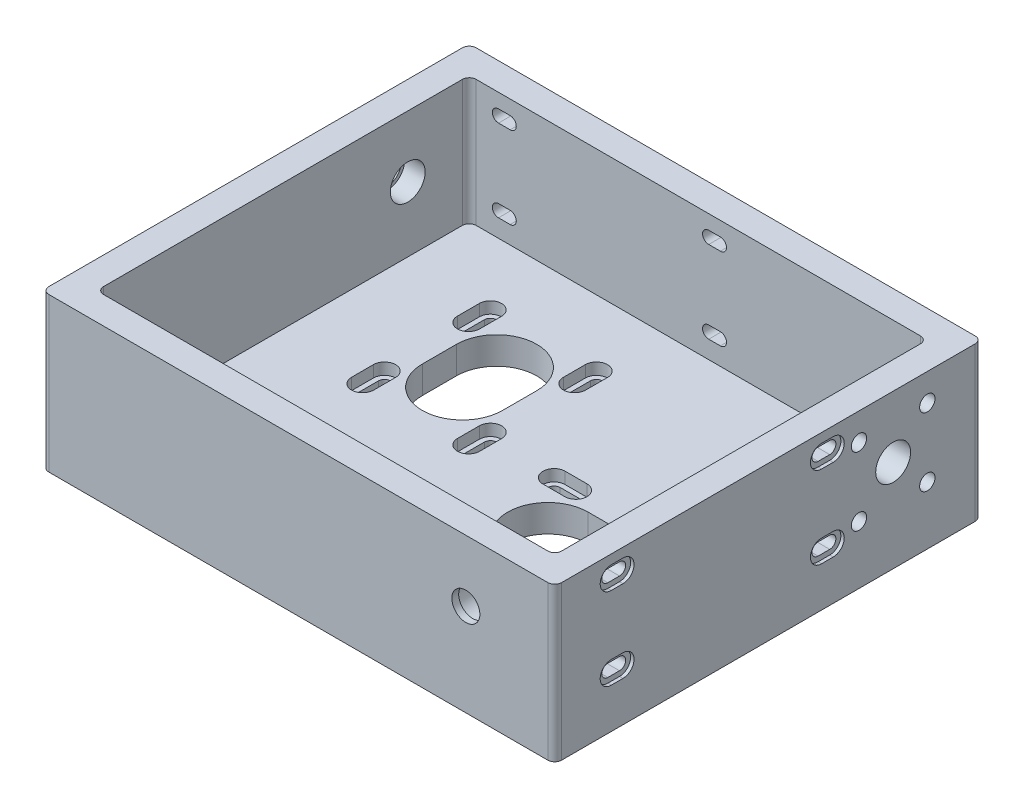
SolidWorks part; units mm, degrees
ref_plane "前基準面" through (0, 0, 0) normal (0, 0, 1) x (1, 0, 0)
ref_plane "上基準面" through (0, 0, 0) normal (0, 1, 0) x (1, 0, 0)
ref_plane "右基準面" through (0, 0, 0) normal (1, 0, 0) x (0, 0, -1)
sketch "草圖1" plane through (0, 0, 0) normal (0, 1, 0) x (1, 0, 0)
  line L1 (-75, -62.5) -> (75, -62.5)
  line L2 (-75, -62.5) -> (-75, 62.5)
  line L3 (-75, 62.5) -> (75, 62.5)
  line L4 (75, -62.5) -> (75, 62.5)
  line L5 (-75, -62.5) -> (75, 62.5) construction
  line L6 (-75, 62.5) -> (75, -62.5) construction
  point P0 (0, 0)
  dimension "D1" = 125
  dimension "D2" = 150
extrude "填料-伸長1" add sketch "草圖1" along normal blind 45
shell "薄殼1" thickness 8 removed face at (0, 45, 0)
sketch "草圖5" plane through (0, 0, 62.5) normal (0, 0, 1) x (1, 0, 0)
  line L0 (67, 45) -> (67, 8) construction
  line L3 (-67, 45) -> (67, 45) construction
  circle A0 centre (49, 27) radius 5.1
  dimension "D3" = 10.2
  dimension "D1" = 18
  dimension "D2" = 18
extrude "除料-伸長1" cut sketch "草圖5" against normal up to next
sketch "草圖6" plane through (-75, 0, 0) normal (-1, 0, 0) x (0, 0, 1)
  line L0 (54.5, 32.1) -> (54.5, 21.9) construction
  line L1 (54.5, 32.1) -> (54.5, 21.9) construction
  line L2 (54.5, 27) -> (-36.5, 27) construction
  line L3 (-54.5, 45) -> (-54.5, 8) construction
  line L4 (-36.5, 32.1) -> (-36.5, 21.9) construction
  circle A0 centre (-36.5, 27) radius 5.1
  dimension "D1" = 18
extrude "除料-伸長2" cut sketch "草圖6" against normal through all
sketch "草圖7" plane through (0, 8, 0) normal (0, 1, 0) x (1, 0, 0)
  line L0 (-26, 21.5) -> (-26, 11.5) construction
  line L1 (-14.25, 21.5) -> (-14.25, 11.5)
  line L2 (-37.75, 21.5) -> (-37.75, 11.5)
  line L3 (24, -13.5) -> (34, -13.5) construction
  line L4 (24, -1.75) -> (34, -1.75)
  line L5 (24, -25.25) -> (34, -25.25)
  arc A0 (-14.25, 21.5) -> (-37.75, 21.5) centre (-26, 21.5) ccw
  arc A1 (-37.75, 11.5) -> (-14.25, 11.5) centre (-26, 11.5) ccw
  arc A3 (24, -1.75) -> (24, -25.25) centre (24, -13.5) ccw
  arc A4 (34, -25.25) -> (34, -1.75) centre (34, -13.5) ccw
  circle A5 centre (29, -13.5) radius 11.75 construction
  point P2 (-26, 16.5)
  point P12 (29, -13.5)
  dimension "D1" = 10
extrude "除料-伸長3" cut sketch "草圖7" against normal through all
hole_wizard "M3 六角承窩頭蓋螺釘的柱孔2" positions "草圖8" profile "草圖9" size "M3" standard "ISO" slot yes
sketch "草圖8" plane through (0, 8, 0) normal (0, 1, 0) x (1, 0, 0)
  line L0 (-10.5, 27) -> (-10.5, 37) construction
  point P0 (-10.5, 32)
  point P5 (-10.5, 1)
  point P8 (-41.5, 1)
  point P11 (-41.5, 32)
  dimension "D1" = 10
sketch "草圖9" plane through (-10.5, 8, -32) normal (1, 0, 0) x (0, 0, 1)
  line L0 (0, 0) -> (0, 11.0815)
  line L1 (0, 11.0815) -> (1.8, 10)
  line L2 (1.8, 10) -> (1.8, 3.4)
  line L3 (1.8, 3.4) -> (3.25, 3.4)
  line L4 (3.25, 3.4) -> (3.25, 0)
  line L5 (3.25, 0) -> (0, 0)
  line L10 (0, 11.0815) -> (-1.8, 10) construction
  line L11 (0, -6.35) -> (0, 107.95) construction
  dimension "鑽孔直徑" = 3.6
  dimension "鑽孔深度" = 10
  dimension "柱孔直徑" = 6.5
  dimension "柱孔深度" = 3.4
  dimension "導頭角度" = 118
hole_wizard "M3 六角承窩頭蓋螺釘的柱孔1" positions "草圖10" profile "草圖11" size "M3" standard "ISO" slot yes end condition through all
sketch "草圖10" plane through (0, 8, 0) normal (0, 1, 0) x (1, 0, 0)
  line L0 (39.5, 2) -> (49.5, 2) construction
  point P0 (44.5, 2)
  point P4 (44.5, -29)
  point P7 (13.5, 2)
  point P10 (13.5, -29)
  dimension "D1" = 10
sketch "草圖11" plane through (44.5, 8, -2) normal (1, 0, 0) x (0, 0, 1)
  line L0 (0, 0) -> (0, 8)
  line L1 (0, 8) -> (1.8, 8)
  line L3 (1.8, 8) -> (1.8, 3.4)
  line L4 (1.8, 3.4) -> (3.25, 3.4)
  line L5 (3.25, 3.4) -> (3.25, 0)
  line L7 (3.25, 0) -> (0, 0)
  line L11 (0, -6.35) -> (0, 107.95) construction
  dimension "貫穿孔直徑" = 3.6
  dimension "貫穿孔深度" = 8
  dimension "柱孔直徑" = 6.5
  dimension "柱孔深度" = 3.4
hole_wizard "M3 六角承窩頭蓋螺釘的柱孔4" positions "草圖12" profile "草圖14" size "M3" standard "ISO" slot yes end condition up to next
sketch "草圖12" plane through (0, 0, -62.5) normal (0, 0, -1) x (-1, 0, 0)
  line L0 (60.25, 39) -> (53.25, 39) construction
  point P0 (56.75, 39)
  point P3 (56.75, 15)
  point P9 (-4.75, 39)
  point P12 (-4.75, 15)
  dimension "D1" = 7
sketch "草圖14" plane through (-56.75, 39, -62.5) normal (1, 0, 0) x (0, 1, 0)
  line L0 (0, 0) -> (0, 8)
  line L1 (0, 8) -> (1.8, 8)
  line L3 (1.8, 8) -> (1.8, 1)
  line L4 (1.8, 1) -> (3.25, 1)
  line L5 (3.25, 1) -> (3.25, 0)
  line L7 (3.25, 0) -> (0, 0)
  line L11 (0, -6.35) -> (0, 107.95) construction
  dimension "貫穿孔直徑" = 3.6
  dimension "貫穿孔深度" = 8
  dimension "柱孔直徑" = 6.5
  dimension "柱孔深度" = 1
hole_wizard "M3 六角承窩頭蓋螺釘的柱孔5" positions "草圖15" profile "草圖16" size "M3" standard "ISO" slot yes end condition up to next
sketch "草圖15" plane through (75, 0, 0) normal (1, 0, 0) x (0, 0, -1)
  line L0 (20.75, 39) -> (13.75, 39) construction
  point P0 (17.25, 39)
  point P5 (17.25, 15)
  point P8 (-44.25, 15)
  point P11 (-44.25, 39)
  dimension "D1" = 7
sketch "草圖16" plane through (75, 39, -17.25) normal (0, 1, 0) x (0, 0, -1)
  line L0 (0, 0) -> (0, 8)
  line L1 (0, 8) -> (1.8, 8)
  line L3 (1.8, 8) -> (1.8, 1)
  line L4 (1.8, 1) -> (3.25, 1)
  line L5 (3.25, 1) -> (3.25, 0)
  line L7 (3.25, 0) -> (0, 0)
  line L11 (0, -6.35) -> (0, 107.95) construction
  dimension "貫穿孔直徑" = 3.6
  dimension "貫穿孔深度" = 8
  dimension "柱孔直徑" = 6.5
  dimension "柱孔深度" = 1
fillet "圓角1" radius 2 4 edges at (67, 26.5, 54.5) (67, 26.5, -54.5) (-67, 26.5, -54.5) (-67, 26.5, 54.5)
fillet "圓角2" radius 2 4 edges at (75, 22.5, 62.5) (-75, 22.5, -62.5) (75, 22.5, -62.5) (-75, 22.5, 62.5)
sketch "草圖17" plane through (75, 0, 0) normal (1, 0, 0) x (0, 0, -1)
  line L1 (26.5, 37) -> (46.5, 37) construction
  line L2 (26.5, 37) -> (26.5, 17) construction
  line L3 (26.5, 17) -> (46.5, 17) construction
  line L4 (46.5, 37) -> (46.5, 17) construction
  line L5 (26.5, 37) -> (46.5, 17) construction
  line L6 (26.5, 17) -> (46.5, 37) construction
  circle A0 centre (26.5, 37) radius 2.25
  circle A1 centre (46.5, 37) radius 2.25
  circle A2 centre (46.5, 17) radius 2.25
  circle A3 centre (26.5, 17) radius 2.25
  point P0 (36.5, 27)
  point P15 (36.5, 27)
  dimension "D3" = 4.5
  dimension "D1" = 20
  dimension "D2" = 4
extrude "除料-伸長4" cut sketch "草圖17" against normal up to next
sketch "草圖18" plane through (0, 0, 62.5) normal (0, 0, 1) x (1, 0, 0)
  circle A0 centre (49, 27) radius 5.1 construction
  circle A1 centre (49, 27) radius 5.1
  circle A2 centre (49, 27) radius 4.1
  dimension "D1" = 1
extrude "填料-伸長2" add sketch "草圖18" against normal blind 2
sketch "草圖19" plane through (-75, 0, 0) normal (-1, 0, 0) x (0, 0, 1)
  circle A0 centre (-36.5, 27) radius 5.1 construction
  circle A1 centre (-36.5, 27) radius 5.1
  circle A2 centre (-36.5, 27) radius 4.1
  dimension "D1" = 1
extrude "填料-伸長3" add sketch "草圖19" against normal blind 2
